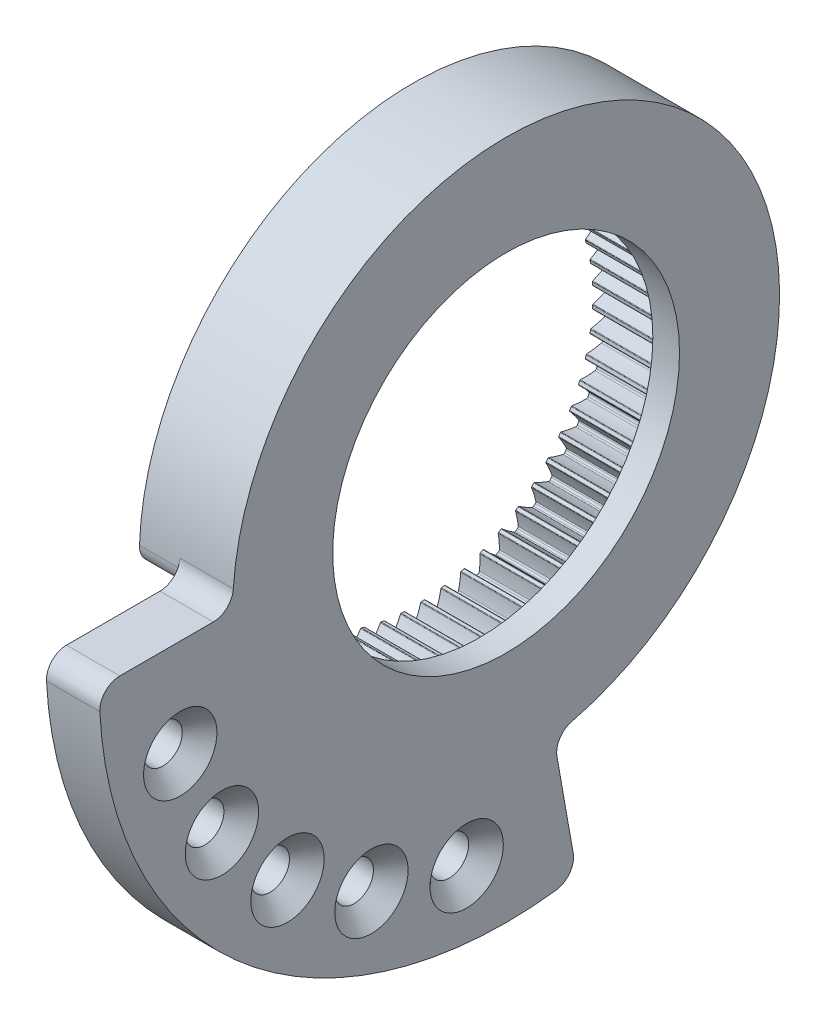
SolidWorks part; units mm, degrees
ref_plane "Plane1" through (0, 0, 0) normal (0, 0, 1) x (1, 0, 0)
ref_plane "Plane2" through (0, 0, 0) normal (0, 1, 0) x (1, 0, 0)
ref_plane "Plane3" through (0, 0, 0) normal (1, 0, 0) x (0, 0, -1)
other "Configuration Table"
sketch "HoldingSke" plane through (0, 0, 0) normal (0, 1, 0) x (1, 0, 0)
  line L0 (0, 0) -> (1.1184, -1.6581)
  line L1 (-15, 0) -> (100, 0) construction
  line L2 (0, 0) -> (-2.1039, 2.3779)
  line L3 (0, 0) -> (-11.863, 4.5341)
  line L4 (0, 0) -> (4.8292, 7.1596)
  line L5 (0, 0) -> (-23.7986, -8.8762)
  line L6 (0, 0) -> (-10.5278, -7.1032)
  line L7 (-2.1039, 2.3779) -> (3.3635, 27.1825)
  line L8 (-76.2, 2.8779) -> (-54.61, 2.8779)
  line L9 (-71.009, 38.7566) -> (-53.1078, 45.2721)
  line L10 (-76.2, 71.12) -> (104.1128, 71.12)
  line L11 (0, 0) -> (-7, 0)
  line L12 (-76.2, 101.6) -> (-76.181, 101.6)
  line L13 (24.9733, 27.94) -> (52.9518, 28.4284)
  line L14 (24.9733, 27.94) -> (24.9743, 27.94)
  line L15 (24.9733, 27.94) -> (100.4006, 29.5858)
  circle A0 centre (0, 0) radius 21
  circle A1 centre (0, 0) radius 12.7
  circle A2 centre (0, 0) radius 12.7
  dimension "Num_teeth" = 56
  dimension "Pitch_radius" = 180.3128
  dimension "Width" = 7
  dimension "Diameter" = 42
sketch "BasProSke" plane through (0, 0, 0) normal (0, 1, 0) x (1, 0, 0)
  line L0 (-10, 0) -> (60, 0) construction
  line L1 (0, 13.5) -> (0, 21)
  line L2 (0, 13.5) -> (7, 13.5)
  line L3 (7, 13.5) -> (7, 21)
  line L4 (7, 21) -> (0, 21)
  dimension "Thickness" = 7
  dimension "Diameter" = 42
revolve "Base-Revolve" add sketch "BasProSke" angle 360 about L0
sketch "TooCutSke" plane through (0, 0, 0) normal (1, 0, 0) x (0, 0, -1)
  line L3 (0.4401, 13.9931) -> (0.4401, 53.6633) construction
  line L4 (0, 0) -> (0, 59.563) construction
  line L5 (0, 0) -> (-3.8312, 68.22) construction
  line L6 (-6.1069, 11.5158) -> (37.1194, 13.9434) construction
  circle A0 centre (0, 0) radius 14 construction
  circle A1 centre (0, 0) radius 14.626 construction
  circle A2 centre (0, 0) radius 11.8401 construction
  circle A3 centre (0, 0) radius 13.4746 construction
  arc A4 (0.6176, 13.4604) -> (0.1647, 14.6251) centre (-6.1069, 11.5158) ccw
  arc A5 (0.6176, 13.4604) -> (-0.6176, 13.4604) centre (0, 0) ccw
  arc A6 (0.1647, 14.6251) -> (-0.1647, 14.6251) centre (0, 0) ccw
  arc A7 (-0.1647, 14.6251) -> (-0.6176, 13.4604) centre (6.1069, 11.5158) ccw
extrude "ToothCut" cut sketch "TooCutSke" along normal through all
fillet "Breaks" radius 0.05 2 edges at (3.5, 13.4862, 0.6101) (3.5, 13.4862, -0.6101)
fillet "RootFillets" radius 0.126 2 edges at (3.5, 14.6251, 0.1647) (3.5, 14.6251, -0.1647)
pattern_circular "TeethCuts" count 56 every 6.429 about axis through (-10, 0, 0) along (1, 0, 0) of "RootFillets", "Breaks", "ToothCut"
sketch "Sketch1" plane through (0, 0, 0) normal (-1, 0, 0) x (0, 0, 1)
  circle A0 centre (0, 0) radius 20.5
  circle A1 centre (0, 0) radius 21
  dimension "1" = 41
extrude "Cut-Extrude1" cut sketch "Sketch1" against normal through all
sketch "Sketch2" plane through (7, 0, 0) normal (1, 0, 0) x (0, 0, -1)
  circle A0 centre (0, 0) radius 20.5
  circle A1 centre (0, 0) radius 13
  dimension "7.5" = 26
extrude "Boss-Extrude1" add sketch "Sketch2" against normal blind 2
sketch "Sketch3" plane through (0, 0, 0) normal (-1, 0, 0) x (0, 0, 1)
  line L0 (0, 0) -> (28.6774, 0) construction
  line L1 (0, 0) -> (28.6446, -8.5756) construction
  line L2 (20.5, 0) -> (30.5, 0)
  line L3 (-3.5618, -20.1882) -> (-5.2982, -30.0363)
  arc A0 (-3.5618, -20.1882) -> (20.5, 0) centre (0, 0) ccw
  arc A1 (30.5, 0) -> (-5.2982, -30.0363) centre (0, 0) cw
  circle A2 centre (0, 0) radius 20.5 construction
  arc A3 (-3.5618, -20.1882) -> (20.5, 0) centre (0, 0) ccw
  dimension "D3" = 30.5
  dimension "D4" = 0
  dimension "D1" = 16.667
  dimension "D2" = 100
  dimension "D5" = 10
  dimension "D6" = 10
  dimension "D7" = 46.73
extrude "Boss-Extrude2" add sketch "Sketch3" against normal up to surface (7 mm away) contours A1 L2 A0 L3
sketch "Sketch4" plane through (0, 0, 0) normal (-1, 0, 0) x (0, 0, 1)
  line L0 (0, 0) -> (29.2843, 0) construction
  line L1 (20.5, 0) -> (30.5, 0) construction
  line L2 (0, 0) -> (24.4287, -7.3135) construction
  circle A0 centre (24.4287, -7.3135) radius 0.5
  circle A1 centre (21.3049, -14.0125) radius 0.5
  circle A2 centre (16.3911, -19.5341) radius 0.5
  circle A3 centre (10.1, -23.4145) radius 0.5
  circle A4 centre (2.9604, -25.3276) radius 0.5
  arc A5 (20.5, 0) -> (-3.5618, -20.1882) centre (0, 0) ccw construction
  point P18 (0, 0)
  dimension "D2" = 1
  dimension "D1" = 16.667
  dimension "D3" = 25.5
  dimension "D4" = 5
extrude "Cut-Extrude2" cut sketch "Sketch4" against normal through all
sketch "Sketch5" plane through (0, 0, 0) normal (-1, 0, 0) x (0, 0, 1)
  line L0 (-3.5618, -20.1882) -> (-0.9266, -17.977)
  line L1 (20.5, 0) -> (17.8648, -2.2112)
  line L2 (20.5, 0) -> (30.5, 0) construction
  line L3 (-3.5618, -20.1882) -> (-5.2982, -30.0363) construction
  line L4 (-3.5618, -20.1882) -> (-5.2982, -30.0363)
  line L5 (20.5, 0) -> (30.5, 0)
  arc A0 (-0.9266, -17.977) -> (17.8648, -2.2112) centre (0.001, -0.0009) ccw
  arc A1 (30.5, 0) -> (-5.2982, -30.0363) centre (0, 0) cw
  dimension "D5" = 18
  dimension "D1" = 140
  dimension "D2" = 140
  dimension "D3" = 3.44
  dimension "D4" = 3.44
extrude "Cut-Extrude3" cut sketch "Sketch5" against normal blind 3
fillet "Fillet1" radius 1.5 6 edges at (5, 0, 30.5) (5, 0, 20.5) (1.5, -2.2112, 17.8648) (1.5, -17.977, -0.9266) (5, -30.0363, -5.2982) (5, -20.1882, -3.5618)
fillet "Fillet2" radius 1.5 2 edges at (1.5, -20.1882, -3.5618) (1.5, 0, 20.5)
hole_wizard "CSK for M2.5 Flat Head Machine Screw1" positions "3DSketch1" profile "Sketch6" countersink size "M2.5" standard "ANSI Metric"
sketch3d "3DSketch1"
  line L0 (7, -7.3135, 24.4287) -> (3, -7.3135, 24.4287) construction
  line L1 (7, -14.0125, 21.3049) -> (3, -14.0125, 21.3049) construction
  line L2 (7, -19.5341, 16.3911) -> (3, -19.5341, 16.3911) construction
  line L3 (7, -23.4145, 10.1) -> (3, -23.4145, 10.1) construction
  line L4 (7, -25.3276, 2.9604) -> (3, -25.3276, 2.9604) construction
  point P0 (7, -7.3135, 24.4287)
  point P4 (7, -14.0125, 21.3049)
  point P8 (26.7848, -25.6269, 0)
  point P10 (7, -19.5341, 16.3911)
  point P14 (7, -23.4145, 10.1)
  point P18 (7, -25.3276, 2.9604)
sketch "Sketch6" plane through (7, -7.3135, 24.4287) normal (0, 1, 0) x (0, 0, -1)
  line L0 (0, 0) -> (0, 7)
  line L1 (0, 7) -> (1.45, 7)
  line L2 (1.45, 7) -> (1.45, 1.3)
  line L3 (1.45, 1.3) -> (2.75, 0)
  line L5 (2.75, 0) -> (0, 0)
  line L6 (-1.45, 1.3) -> (-2.75, 0) construction
  line L11 (0, -6.35) -> (0, 107.95) construction
  dimension "Thru Hole Dia." = 2.9
  dimension "Thru Hole Depth" = 7
  dimension "Near C'Sink Dia." = 5.5
  dimension "Near C'Sink Angle" = 90
equation "' \"Module@HoldingSke\" = 6.35"
equation "' \"Num_teeth@HoldingSke\" = 24"
equation "' \"Ap@HoldingSke\" =  14.5"
equation "' \"Ap@HoldingSke\" = 14.5"
equation "' \"Width@HoldingSke\" = 12"
equation "' \"Diameter@HoldingSke\" = 8 * 25.4"
equation "' \"Show_teeth@HoldingSke\" = 100"
equation "' \"Backlash@HoldingSke\" = 0.009 * 25.4"
equation "' \"Addendum_fac@HoldingSke\" = 1.0"
equation "' \"Dedendum_fac@HoldingSke\" = 1.25"
equation "' \"Dedendum_add@HoldingSke\" = 0.00005 * 25.4"
equation "' \"Clearance_fac@HoldingSke\" = 0.25"
equation "\"Pitch@HoldingSke\" = 1 / \"Module@HoldingSke\" "
equation "\"Overcut_dia@TooCutSke\" = (\"Num_teeth@HoldingSke\" - 2 * \"Addendum_fac@HoldingSke\") / \"Pitch@HoldingSke\" - 0.002 * 25.4"
equation "\"Pitch_dia@TooCutSke\" = \"Num_teeth@HoldingSke\" / \"Pitch@HoldingSke\""
equation "\"Base_dia@TooCutSke\" = \"Num_teeth@HoldingSke\" / \"Pitch@HoldingSke\" * cos((\"Ap@HoldingSke\"  * 3.14159265 / 180)) * 0.90"
equation "\"Root_dia@TooCutSke\" = \"Num_teeth@HoldingSke\"  / \"Pitch@HoldingSke\" + 2 *  \"Dedendum_fac@HoldingSke\"/ \"Pitch@HoldingSke\" + \"Dedendum_add@HoldingSke\" * 2"
equation "\"Half_ang@TooCutSke\" = 180 / \"Num_teeth@HoldingSke\""
equation "\"Half_CT@TooCutSke\" = \"Num_teeth@HoldingSke\" / \"Pitch@HoldingSke\" * sin((3.14159265 / 2 / \"Num_teeth@HoldingSke\")) / 2 + 10 * \"Backlash@HoldingSke\" / 4"
equation "\"Flank_rad@TooCutSke\" = \"Num_teeth@HoldingSke\" / \"Pitch@HoldingSke\" / 4"
equation "\"Radius@RootFillets\"= \"Clearance_fac@HoldingSke\" / \"Pitch@HoldingSke\" + \"Dedendum_add@HoldingSke\""
equation "\"Break_rad@Breaks\" = 0.02 / \"Pitch@HoldingSke\" * 5"
equation "\"Num_teeth@TeethCuts\" = int( \"Show_teeth@HoldingSke\" ) + 1"
equation "\"Num_teeth@TeethCuts\" = ((sgn( \"Num_teeth@TeethCuts\" - \"Num_teeth@HoldingSke\" )-1)*( \"Num_teeth@TeethCuts\" - \"Num_teeth@HoldingSke\" ))/-2+ \"Num_teeth@HoldingSke\""
equation "\"Num_teeth@TeethCuts\" = ((sgn( \"Num_teeth@TeethCuts\" - 2.0)+1)*( \"Num_teeth@TeethCuts\" - 2.0))/2 +2.0"
equation "\"Angle@TeethCuts\" = 360.0 / \"Num_teeth@HoldingSke\""
equation "\"Diameter@BasProSke\" = \"Num_teeth@HoldingSke\"  / \"Pitch@HoldingSke\" + 2 *  \"Dedendum_fac@HoldingSke\"/ \"Pitch@HoldingSke\" + \"Dedendum_add@HoldingSke\" * 2 + 0.002 * 25.4"
equation "\"Diameter@BasProSke\" = ((sgn( \"Diameter@BasProSke\"  - \"Diameter@HoldingSke\" )+1)*( \"Diameter@BasProSke\"  - \"Diameter@HoldingSke\" ))/2 + \"Diameter@HoldingSke\""
equation "\"Inside_diameter@BasProSke\" =  (\"Num_teeth@HoldingSke\" - 2 * \"Addendum_fac@HoldingSke\") / \"Pitch@HoldingSke\" "
equation "\"Thickness@BasProSke\"  = \"Width@HoldingSke\""
